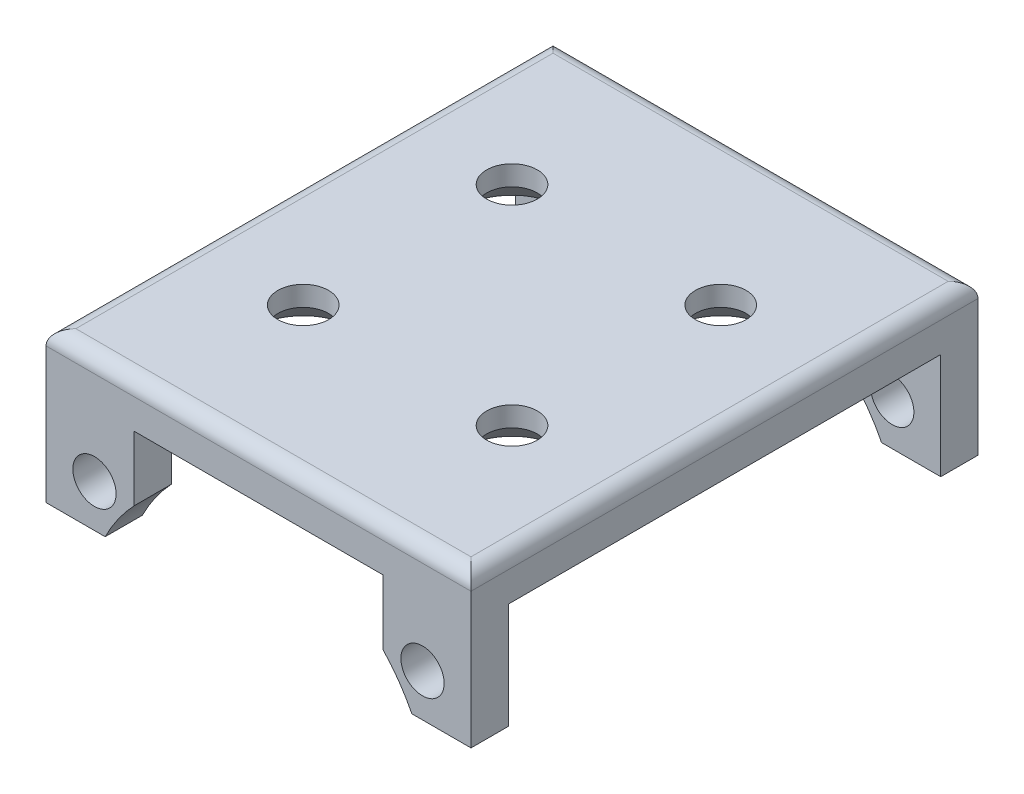
SolidWorks part; units mm, degrees
ref_plane "Front Plane" through (0, 0, 0) normal (0, 0, 1) x (1, 0, 0)
ref_plane "Top Plane" through (0, 0, 0) normal (0, 1, 0) x (1, 0, 0)
ref_plane "Right Plane" through (0, 0, 0) normal (1, 0, 0) x (0, 0, -1)
sketch "Sketch1" plane through (0, 0, 0) normal (0, 0, 1) x (1, 0, 0)
  line L0 (0, 0) -> (0, 5.0753) construction
  line L1 (-14.25, 11.25) -> (14.25, 11.25)
  line L2 (-14.25, 11.25) -> (-14.25, -35.25)
  line L3 (-14.25, -35.25) -> (14.25, -35.25)
  line L4 (14.25, 11.25) -> (14.25, -35.25)
  line L5 (-14.25, 11.25) -> (-7.75, 11.25)
  line L6 (-14.25, 11.25) -> (-14.25, 4.75)
  line L7 (-14.25, 4.75) -> (-7.75, 4.75)
  line L8 (-7.75, 11.25) -> (-7.75, 4.75)
  line L9 (0, 0) -> (3.7441, 0) construction
  line L10 (14.25, 4.75) -> (7.75, 4.75)
  line L11 (7.75, 11.25) -> (7.75, 4.75)
  line L12 (-14.25, -12) -> (23.601, -12) construction
  line L13 (7.75, -35.25) -> (7.75, -29.75)
  line L14 (14.25, -28.75) -> (8.75, -28.75)
  line L15 (-7.75, -35.25) -> (-7.75, -29.75)
  line L16 (-14.25, -28.75) -> (-8.75, -28.75)
  line L18 (14.25, 11.25) -> (-14.25, 11.25)
  line L19 (14.25, 11.25) -> (14.25, 15.25)
  line L20 (14.25, 15.25) -> (-14.25, 15.25)
  line L21 (-14.25, 11.25) -> (-14.25, 15.25)
  line L22 (-14.25, 4.75) -> (-16.25, 4.75)
  line L23 (-14.25, 4.75) -> (-14.25, 15.25)
  line L24 (-14.25, 15.25) -> (-16.25, 15.25)
  line L25 (-16.25, 4.75) -> (-16.25, 15.25)
  line L26 (14.25, 15.25) -> (16.25, 15.25)
  line L27 (14.25, 15.25) -> (14.25, 4.75)
  line L28 (14.25, 4.75) -> (16.25, 4.75)
  line L29 (16.25, 15.25) -> (16.25, 4.75)
  line L30 (-8.25, 11.25) -> (8.25, 11.25)
  line L31 (-8.25, 11.25) -> (-8.25, 4.75)
  line L32 (-8.25, 4.75) -> (8.25, 4.75)
  line L33 (8.25, 11.25) -> (8.25, 4.75)
  line L34 (-8.25, 11.25) -> (8.25, 11.25)
  line L35 (-8.25, 11.25) -> (-8.25, 12.25)
  line L36 (-8.25, 12.25) -> (8.25, 12.25)
  line L37 (8.25, 11.25) -> (8.25, 12.25)
  circle A1 centre (0, 0) radius 10.45
  circle A2 centre (-11, 8) radius 1.45
  circle A3 centre (11, 8) radius 1.45
  circle A4 centre (11, -32) radius 1.45
  circle A5 centre (-11, -32) radius 1.45
  arc A7 (-7.75, -29.75) -> (-8.75, -28.75) centre (-8.75, -29.75) ccw
  arc A8 (8.75, -28.75) -> (7.75, -29.75) centre (8.75, -29.75) ccw
  circle A9 centre (0, 0) radius 11.5
  point P0 (0, 0)
  point P35 (-7.75, -28.75)
  point P38 (7.75, -28.75)
  dimension "D1" = 28.5
  dimension "D2" = 46.5
  dimension "D3" = 23
  dimension "D4" = 11.25
  dimension "D5" = 2.9
  dimension "D6" = 3.25
  dimension "D7" = 3.25
  dimension "D10" = 3.25
  dimension "D12" = 1
  dimension "D16" = 20.9
  dimension "D17" = 0.5
  dimension "D11" = 3.25
  dimension "D13" = 4
  dimension "D14" = 2
  dimension "D15" = 2
  dimension "D18" = 0.5
  dimension "D19" = 1
  dimension "D8" = 2
  dimension "D9" = 2
extrude "Boss-Extrude7" add sketch "Sketch1" along normal blind 17 and the other way blind 17 contours L37 L18 L19 L20 L21 L1 L35 L36 | A9 L10 L4 L18 L33 A3 | A9 L31 L1 L2 L7 A2 region at (0, 13.5038, 0) region at (-11.25, 11.1615, 0) region at (14.1615, 8, 0)
sketch "Sketch34" plane through (-14.25, 0, 0) normal (-1, 0, 0) x (0, 0, 1)
  line L0 (-17, 4.75) -> (17, 4.75) construction
  line L1 (-14.2, 12.25) -> (14.2, 12.25)
  line L2 (-14.2, 12.25) -> (-14.2, 4.75)
  line L3 (-14.2, 4.75) -> (14.2, 4.75)
  line L4 (14.2, 12.25) -> (14.2, 4.75)
  line L5 (-17, 4.75) -> (-17, 15.25) construction
  line L6 (17, 4.75) -> (17, 15.25) construction
  line L7 (-17, 15.25) -> (17, 15.25) construction
  dimension "D1" = 2.8
  dimension "D2" = 2.8
  dimension "D3" = 3
extrude "Cut-Extrude11" cut sketch "Sketch34" against normal through all
sketch "Sketch35" plane through (0, 15.25, 0) normal (0, 1, 0) x (1, 0, 0)
  circle A0 centre (0, 0) radius 5
extrude "Cut-Extrude12" cut sketch "Sketch35" against normal through all
sketch "Sketch39" plane through (0, 12.25, 0) normal (0, -1, 0) x (1, 0, 0)
  line L0 (-14.25, 14.2) -> (-14.25, -14.2) construction
  line L1 (-8.25, 17) -> (8.25, 17) construction
  line L3 (0, 0) -> (0, 7.1623) construction
  line L4 (0, 0) -> (6.1391, 0) construction
  circle A0 centre (-8.25, 9) radius 1.5
  circle A1 centre (8.25, 9) radius 1.5
  circle A2 centre (-8.25, -9) radius 1.5
  circle A3 centre (8.25, -9) radius 1.5
  point P0 (-8.25, 9)
  point P9 (8.25, 9)
  point P12 (-8.25, -9)
  point P14 (8.25, -9)
  dimension "D1" = 6
  dimension "D2" = 8
hole_wizard "CSK for M3 Hex Socket Countersunk Cap Screw3" positions "Sketch39" profile "Sketch40" countersink size "M3" standard "ISO" end condition through all
sketch "Sketch40" plane through (-8.25, 12.25, 9) normal (1, 0, 0) x (0, 0, -1)
  line L0 (0, 0) -> (0, 3)
  line L1 (0, 3) -> (1.7, 3)
  line L2 (1.7, 3) -> (1.7, 1.66)
  line L3 (1.7, 1.66) -> (3.36, 0)
  line L5 (3.36, 0) -> (0, 0)
  line L6 (-1.7, 1.66) -> (-3.36, 0) construction
  line L11 (0, -6.35) -> (0, 107.95) construction
  dimension "Thru Hole Dia." = 3.4
  dimension "Thru Hole Depth" = 3
  dimension "Near C'Sink Dia." = 6.72
  dimension "Near C'Sink Angle" = 90
fillet "Fillet5" radius 1 4 edges at (14.25, 15.25, 0) (-14.25, 15.25, 0) (0, 15.25, -17) (0, 15.25, 17)
sketch "Sketch41" plane through (0, 0, 17) normal (0, 0, 1) x (1, 0, 0)
  line L0 (14.25, 4.75) -> (14.25, 14.25) construction
  line L1 (-14.25, 4.75) -> (14.25, 4.75)
  line L2 (-14.25, 4.75) -> (-14.25, 5.15)
  line L3 (-14.25, 5.15) -> (14.25, 5.15)
  line L4 (14.25, 4.75) -> (14.25, 5.15)
  dimension "D1" = 0.4
extrude "Cut-Extrude13" cut sketch "Sketch41" against normal through all
sketch "Sketch45" plane through (0, 0, 17) normal (0, 0, 1) x (1, 0, 0)
  circle A0 centre (11, 8) radius 1.45
  circle A1 centre (0, 0) radius 11.5
sketch "Sketch47" plane through (0, 15.25, 0) normal (0, 1, 0) x (1, 0, 0)
  line L1 (12, -14) -> (-12, -14)
  line L2 (12, -14) -> (12, 14)
  line L3 (12, 14) -> (-12, 14)
  line L4 (-12, -14) -> (-12, 14)
  line L5 (12, -14) -> (-12, 14) construction
  line L6 (12, 14) -> (-12, -14) construction
  point P0 (0, 0)
  dimension "D1" = 24
  dimension "D2" = 28
extrude "Boss-Extrude8" add sketch "Sketch47" against normal blind 3
sketch "Sketch49" plane through (0, 12.25, 0) normal (0, -1, 0) x (1, 0, 0)
  line L0 (-8.25, 17) -> (8.25, 17) construction
  line L5 (-14.25, 14.2) -> (-14.25, -14.2) construction
  line L6 (-8.25, -17) -> (8.25, -17) construction
  circle A0 centre (-7, 7) radius 1.5
  circle A1 centre (7, 7) radius 1.5
  circle A2 centre (7, -7) radius 1.5
  circle A3 centre (-7, -7) radius 1.5
  point P0 (0, 0)
  point P18 (-7, 7)
  point P21 (-7, -7)
  point P24 (7, -7)
  point P27 (7, 7)
  dimension "D3" = 2
  dimension "D1" = 10
  dimension "D2" = 7.25
  dimension "D5" = 7.25
  dimension "D6" = 10
  dimension "D4" = 2
hole_wizard "CSK for M3 Hex Socket Countersunk Cap Screw4" positions "Sketch49" profile "Sketch50" countersink size "M3" standard "ISO" end condition through all
sketch "Sketch50" plane through (0, 12.25, 0) normal (1, 0, 0) x (0, 0, -1)
  line L0 (0, 0) -> (0, 3)
  line L1 (0, 3) -> (1.7, 3)
  line L2 (1.7, 3) -> (1.7, 1.66)
  line L3 (1.7, 1.66) -> (3.36, 0)
  line L5 (3.36, 0) -> (0, 0)
  line L6 (-1.7, 1.66) -> (-3.36, 0) construction
  line L11 (0, -6.35) -> (0, 107.95) construction
  dimension "Thru Hole Dia." = 3.4
  dimension "Thru Hole Depth" = 3
  dimension "Near C'Sink Dia." = 6.72
  dimension "Near C'Sink Angle" = 90
sketch "Sketch51" plane through (0, 12.25, 0) normal (0, -1, 0) x (1, 0, 0)
  line L1 (-4.025, 3.8212) -> (4.025, 3.8212)
  line L2 (-4.025, 3.8212) -> (-4.025, -3.8212)
  line L3 (-4.025, -3.8212) -> (4.025, -3.8212)
  line L4 (4.025, 3.8212) -> (4.025, -3.8212)
  line L5 (-4.025, 3.8212) -> (4.025, -3.8212) construction
  line L6 (-4.025, -3.8212) -> (4.025, 3.8212) construction
  point P0 (0, 0)
extrude "Boss-Extrude9" add sketch "Sketch51" against normal blind 3
sketch "Sketch53" plane through (-14.25, 0, 0) normal (-1, 0, 0) x (0, 0, 1)
  line L0 (-17, 5.15) -> (-14.2, 5.15) construction
  line L1 (-14.5, 5.15) -> (14.5, 5.15)
  line L2 (-14.5, 5.15) -> (-14.5, 12.25)
  line L3 (-14.5, 12.25) -> (14.5, 12.25)
  line L4 (14.5, 5.15) -> (14.5, 12.25)
  line L5 (-14.2, 12.25) -> (-14.2, 5.15) construction
  line L6 (14.2, 5.15) -> (14.2, 12.25) construction
  dimension "D1" = 0.3
  dimension "D2" = 0.3
extrude "Cut-Extrude14" cut sketch "Sketch53" against normal through all
sketch "Sketch54" plane through (0, 0, 17) normal (0, 0, 1) x (1, 0, 0)
  line L0 (-8.25, 8.0117) -> (-8.25, 12.25) construction
  line L1 (-8.35, 12.25) -> (8.35, 12.25)
  line L2 (-8.35, 12.25) -> (-8.35, 6.7019)
  line L3 (-8.35, 6.7019) -> (8.35, 6.7019)
  line L4 (8.35, 12.25) -> (8.35, 6.7019)
  line L5 (8.25, 8.0117) -> (8.25, 12.25) construction
  dimension "D1" = 0.1
  dimension "D2" = 0.1
extrude "Cut-Extrude15" cut sketch "Sketch54" against normal through all
